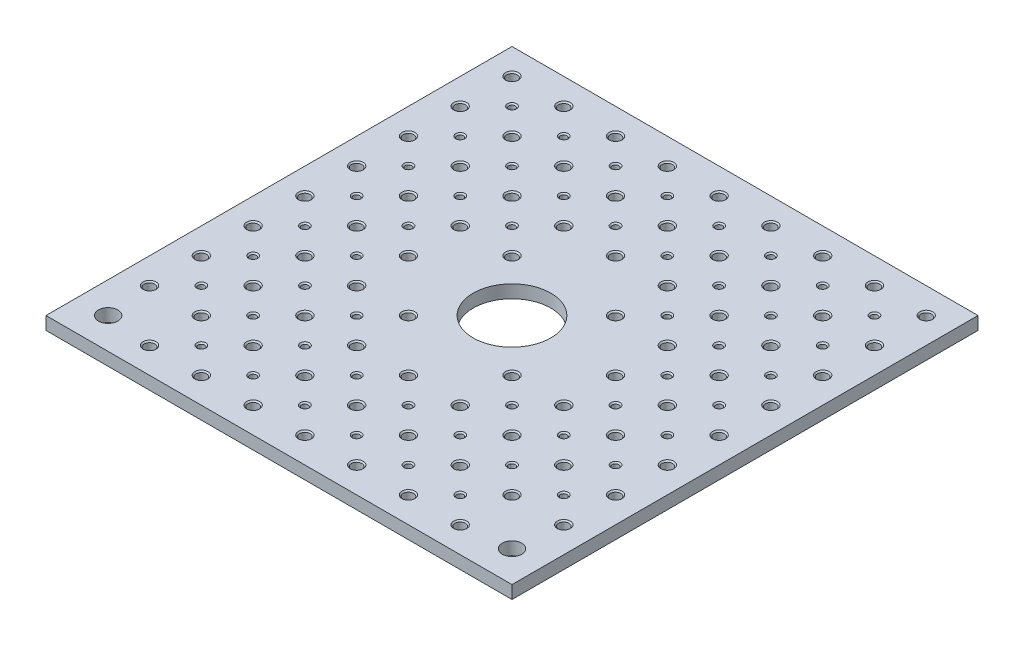
SolidWorks part; units mm, degrees
material "3D Printer - Undefined Plastic"
ref_plane "Front Plane" through (0, 0, 0) normal (0, 0, 1) x (1, 0, 0)
ref_plane "Top Plane" through (0, 0, 0) normal (0, 1, 0) x (1, 0, 0)
ref_plane "Right Plane" through (0, 0, 0) normal (1, 0, 0) x (0, 0, -1)
sketch "Sketch1" plane through (0, 0, 0) normal (0, 1, 0) x (1, 0, 0)
  line L1 (-114.3, -114.3) -> (114.3, -114.3)
  line L2 (-114.3, -114.3) -> (-114.3, 114.3)
  line L3 (-114.3, 114.3) -> (114.3, 114.3)
  line L4 (114.3, -114.3) -> (114.3, 114.3)
  line L5 (-114.3, -114.3) -> (114.3, 114.3) construction
  line L6 (-114.3, 114.3) -> (114.3, -114.3) construction
  point P0 (0, 0)
  dimension "D1" = 228.6
  dimension "D2" = 228.6
extrude "Boss-Extrude1" add sketch "Sketch1" along normal mid plane 6.35
sketch "Sketch2" plane through (0, 3.175, 0) normal (0, 1, 0) x (1, 0, 0)
  circle A0 centre (0, 0) radius 19.05
  dimension "portDiameter" = 38.1
extrude "Cut-Extrude1" cut sketch "Sketch2" against normal through all
hole_wizard "3/8 (0.3750) Dowel Hole1" positions "Sketch5" profile "Sketch6" hole size "3/8" standard "_Gentex Inch" end condition through all
sketch "Sketch5" plane through (0, 3.175, 0) normal (0, 1, 0) x (1, 0, 0)
  line L0 (-99.06, -99.06) -> (99.06, -99.06) construction
  line L2 (-99.06, -99.06) -> (-114.3, -99.06) construction
  line L3 (-114.3, 114.3) -> (-114.3, -114.3) construction
  line L5 (99.06, -99.06) -> (114.3, -99.06) construction
  line L6 (114.3, -114.3) -> (114.3, 114.3) construction
  line L9 (-114.3, -114.3) -> (114.3, -114.3) construction
  circle A0 centre (-99.06, -99.06) radius 15.24 construction
  point P0 (-99.06, -99.06)
  point P2 (99.06, -99.06)
  point P27 (-104.775, -85.1809)
  dimension "pulleyDiameter" = 30.48
  dimension "D1" = 15.24
sketch "Sketch6" plane through (-99.06, 3.175, 99.06) normal (1, 0, 0) x (0, 0, 1)
  line L0 (0, 0) -> (0, 6.35)
  line L1 (0, 6.35) -> (4.7625, 6.35)
  line L2 (4.7625, 6.35) -> (4.7625, 0)
  line L5 (4.7625, 0) -> (0, 0)
  line L11 (0, -6.35) -> (0, 107.95) construction
  dimension "Thru Hole Dia." = 9.525
  dimension "Thru Hole Depth" = 6.35
hole_wizard "Tap Drill for #10 Helicoil3" positions "Sketch7" profile "Sketch8" hole size "#10-32" standard "_Gentex Inch" end condition through all
sketch "Sketch7" plane through (0, 3.175, 0) normal (0, 1, 0) x (1, 0, 0)
  line L0 (-101.6, 101.6) -> (-101.6, 114.3) construction
  line L1 (114.3, 114.3) -> (-114.3, 114.3) construction
  line L3 (-101.6, 101.6) -> (-114.3, 101.6) construction
  line L4 (-114.3, 114.3) -> (-114.3, -114.3) construction
  point P6 (-101.6, 101.6)
  dimension "D1" = 12.7
sketch "Sketch8" plane through (-101.6, 3.175, -101.6) normal (1, 0, 0) x (0, 0, 1)
  line L0 (0, 0) -> (0, 6.35)
  line L1 (0, 6.35) -> (2.5527, 6.35)
  line L2 (2.5527, 6.35) -> (2.5527, 0.635)
  line L3 (2.5527, 0.635) -> (3.1877, 0)
  line L5 (3.1877, 0) -> (0, 0)
  line L6 (-2.5527, 0.635) -> (-3.1877, 0) construction
  line L11 (0, -6.35) -> (0, 107.95) construction
  dimension "Thru Hole Dia." = 5.1054
  dimension "Thru Hole Depth" = 6.35
  dimension "Near C'Sink Dia." = 6.3754
  dimension "Near C'Sink Angle" = 90
cosmetic thread "Cosmetic Thread2" parameters "D1"=6.35, "D2"=6.35
hole_wizard "1/8 (0.1250) Dowel Hole1" positions "Sketch9" profile "Sketch10" hole size "1/8" standard "_Gentex Inch" end condition through all
sketch "Sketch9" plane through (0, 3.175, 0) normal (0, 1, 0) x (1, 0, 0)
  line L1 (-114.3, 114.3) -> (-88.9, 114.3)
  line L2 (-114.3, 114.3) -> (-114.3, 88.9)
  line L3 (-114.3, 88.9) -> (-88.9, 88.9)
  line L4 (-88.9, 114.3) -> (-88.9, 88.9)
  line L5 (-114.3, 114.3) -> (-88.9, 88.9) construction
  line L6 (-114.3, 88.9) -> (-88.9, 114.3) construction
  circle A0 centre (-101.6, 101.6) radius 3.1877 construction
  point P0 (-88.9, 88.9)
  point P79 (-101.6, 101.6)
  point P82 (0, 0)
sketch "Sketch10" plane through (-88.9, 3.175, -88.9) normal (1, 0, 0) x (0, 0, 1)
  line L0 (0, 0) -> (0, 6.35)
  line L1 (0, 6.35) -> (1.5875, 6.35)
  line L2 (1.5875, 6.35) -> (1.5875, 0.635)
  line L3 (1.5875, 0.635) -> (2.2225, 0)
  line L5 (2.2225, 0) -> (0, 0)
  line L6 (-1.5875, 0.635) -> (-2.2225, 0) construction
  line L11 (0, -6.35) -> (0, 107.95) construction
  dimension "Thru Hole Dia." = 3.175
  dimension "Thru Hole Depth" = 6.35
  dimension "Near C'Sink Dia." = 4.445
  dimension "Near C'Sink Angle" = 90
pattern_linear "Thread Hole Pattern" count 9 spacing 25.4 along (1, 0, 0) count 9 spacing 25.4 along (0, 0, 1) skipping (0, 8), (3, 4), (4, 3), (4, 4), (4, 5), (5, 4), (8, 8) of "Tap Drill for #10 Helicoil3"
pattern_linear "Pin Hole Pattern" count 8 spacing 25.4 along (1, 0, 0) count 8 spacing 25.4 along (0, 0, 1) skipping (0, 7), (2, 3), (2, 4), (3, 2), (3, 3), (3, 4), (3, 5), (4, 2), (4, 3), (4, 4), (4, 5), (5, 3), (5, 4), (7, 7) of "1/8 (0.1250) Dowel Hole1"
